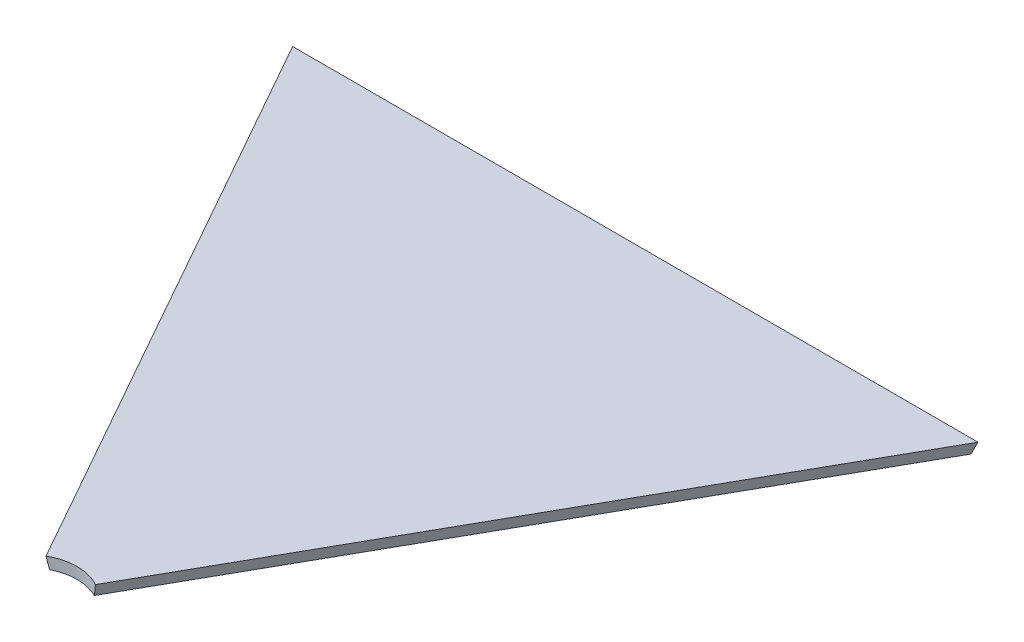
SolidWorks part; units mm, degrees
ref_plane "Front Plane" through (0, 0, 0) normal (0, 0, 1) x (1, 0, 0)
ref_plane "Top Plane" through (0, 0, 0) normal (0, 1, 0) x (1, 0, 0)
ref_plane "Right Plane" through (0, 0, 0) normal (1, 0, 0) x (0, 0, -1)
sketch "Sketch1" plane through (0, 0, 0) normal (0, 1, 0) x (1, 0, 0)
  line L0 (-306, 0) -> (306, 0)
  line L1 (0, 146.6015) -> (0, -695.0802) construction
  line L2 (306, 0) -> (22.0783, -504.1884)
  line L3 (-306, 0) -> (-22.0783, -504.1884)
  arc A0 (22.0783, -504.1884) -> (-22.0783, -504.1884) centre (0, -543.4) ccw
  arc A1 (-22.0783, -504.1884) -> (0, -588.4) centre (0, -543.4) ccw construction
  arc A2 (0, -588.4) -> (22.0783, -504.1884) centre (0, -543.4) ccw construction
  dimension "D2" = 612
  dimension "D3" = 90
  dimension "D1" = 58.77
  dimension "D4" = 543.4
extrude "Boss-Extrude1" add sketch "Sketch1" along normal blind 10
chamfer "Chamfer1" distance 10 angle 13 3 edges at (-164.0392, 0, 252.0942) (0, 0, 0) (164.0392, 0, 252.0942) first distance on face at (-164.0392, 5, 252.0942) first distance on face at (0, 5, 0) first distance on face at (164.0392, 5, 252.0942)
